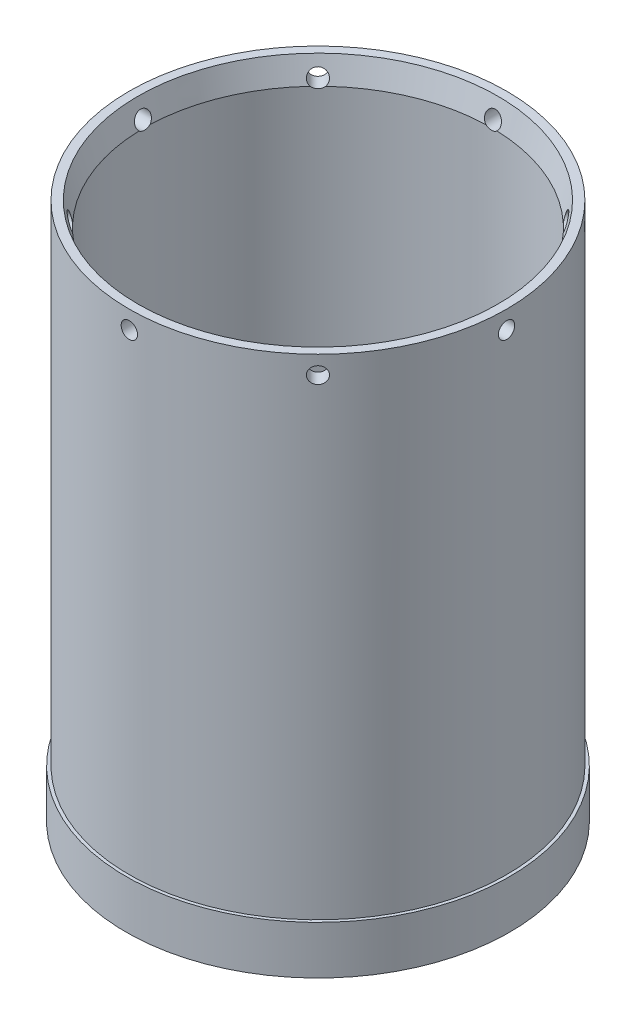
SolidWorks part; units mm, degrees
material "Nylon 101"
ref_plane "Front Plane" through (0, 0, 0) normal (0, 0, 1) x (1, 0, 0)
ref_plane "Top Plane" through (0, 0, 0) normal (0, 1, 0) x (1, 0, 0)
ref_plane "Right Plane" through (0, 0, 0) normal (1, 0, 0) x (0, 0, -1)
sketch "Sketch1" plane through (0, 0, 0) normal (0, 1, 0) x (1, 0, 0)
  circle A0 centre (0, 0) radius 45.72
  circle A1 centre (0, 0) radius 49.72
  dimension "D1" = 91.44
  dimension "D2" = 4
extrude "Boss-Extrude1" add sketch "Sketch1" along normal blind 139.7
sketch "Sketch2" plane through (0, 0, 0) normal (0, -1, 0) x (1, 0, 0)
  circle A1 centre (0, 0) radius 49.72
  circle A2 centre (0, 0) radius 49.72
  dimension "D1" = 0
extrude "Boss-Extrude2" add sketch "Sketch2" along normal blind 2
hole_wizard "#6 Clearance Hole1" positions "3DSketch2" profile "Sketch4" hole size "#6" standard "ANSI Inch"
sketch3d "3DSketch2"
  point P9 (0, 134.9375, 49.72)
  dimension "D1" = 4.7625
sketch "Sketch4" plane through (0, 134.9375, 49.72) normal (1, 0, 0) x (0, -1, 0)
  line L0 (0, 0) -> (0, 26.4394)
  line L1 (0, 26.4394) -> (2.1526, 25.146)
  line L2 (2.1526, 25.146) -> (2.1526, 0)
  line L5 (2.1526, 0) -> (0, 0)
  line L10 (0, 26.4394) -> (-2.1527, 25.146) construction
  line L11 (0, -6.35) -> (0, 107.95) construction
  dimension "Hole Dia." = 4.3053
  dimension "Hole Depth" = 25.146
  dimension "Drill Angle" = 118
pattern_circular "CirPattern1" count 8 over 360 about axis through (0, 139.7, 0) along (0, -1, 0) of "#6 Clearance Hole1"
sketch "Sketch5" plane through (0, -2, 0) normal (0, -1, 0) x (1, 0, 0)
  circle A0 centre (0, 0) radius 50.546
  circle A1 centre (0, 0) radius 49.72 construction
  circle A2 centre (0, 0) radius 49.72
  dimension "D1" = 101.092
extrude "Boss-Extrude3" add sketch "Sketch5" against normal blind 12.7
sketch "Sketch6" plane through (0, 0, 0) normal (0, 1, 0) x (1, 0, 0)
  line L0 (-45.2218, 6.731) -> (-38.8718, 6.731)
  line L1 (-38.8718, 6.731) -> (-38.8718, 3.556)
  line L2 (-38.8718, 3.556) -> (-45.5815, 3.556)
  line L3 (-45.5815, -3.556) -> (-38.8718, -3.556)
  line L4 (-38.8718, -3.556) -> (-38.8718, -6.731)
  line L5 (-38.8718, -6.731) -> (-45.2218, -6.731)
  line L6 (-55, 0) -> (55, 0) construction
  arc A0 (-45.5815, -3.556) -> (-45.2218, -6.731) centre (0, 0) ccw
  circle A1 centre (0, 0) radius 45.72
  arc A2 (-45.2218, 6.731) -> (-45.5815, 3.556) centre (0, 0) ccw
  dimension "D2" = 7.112
  dimension "D3" = 3.556
  dimension "D4" = 3.175
  dimension "D5" = 6.35
extrude "Boss-Extrude4" add sketch "Sketch6" along normal blind 50.8
pattern_circular "CirPattern2" count 2 over 360 about axis through (0, 139.7, 0) along (0, -1, 0) of "Boss-Extrude4" reverse direction yes
chamfer "Chamfer1" distance 6.35 angle 15 1 edges at (0, 139.7, 45.72) first distance on face at (30.8132, 135.43, 33.7767)
equation "\"D1@3DSketch2\"=.375in/2"
equation "\"D3@Sketch6\"=\"D2@Sketch6\"/2"
